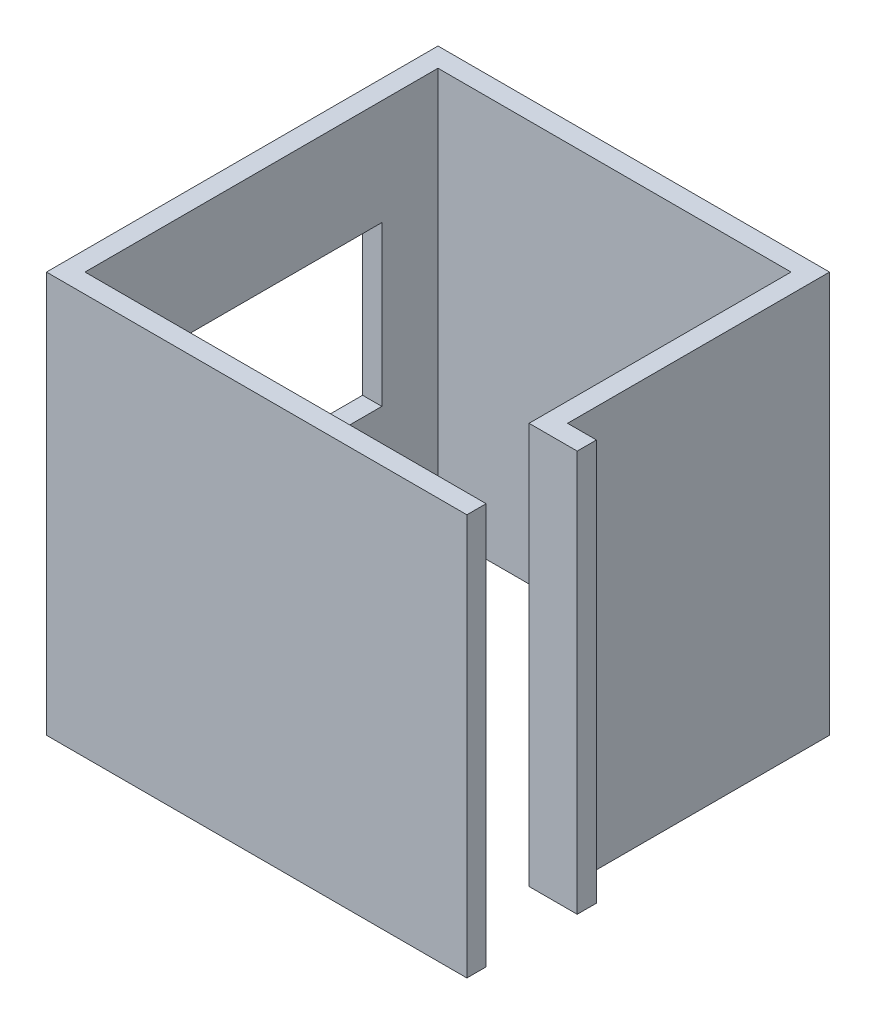
SolidWorks part; units mm, degrees
ref_plane "Спереди" through (0, 0, 0) normal (0, 0, 1) x (1, 0, 0)
ref_plane "Сверху" through (0, 0, 0) normal (0, 1, 0) x (1, 0, 0)
ref_plane "Справа" through (0, 0, 0) normal (1, 0, 0) x (0, 0, -1)
sketch "Эскиз1" plane through (0, 0, 0) normal (0, 1, 0) x (1, 0, 0)
  line L0 (0, 0) -> (0, 2200)
  line L1 (0, 2200) -> (2200, 2200)
  line L2 (2200, 2200) -> (2200, 567.5192)
  line L3 (2200, 567.5192) -> (2500, 567.5192)
  line L4 (0, 0) -> (2500, 0)
  point P4 (282.3103, 2180.8038)
  point P8 (0, 0)
  point P9 (0, 0)
  point P10 (2300, 0)
  point P11 (0, 0)
  point P12 (0, 0)
  point P13 (2500, 0)
extrude "Вытянуть-Тонкостенный1" add sketch "Эскиз1" along normal blind 2500 thin thin type one direction wall 120
sketch "Эскиз2" plane through (-120, 0, 0) normal (-1, 0, 0) x (0, 0, 1)
  line L1 (-1850, 1842.1461) -> (-650, 1842.1461)
  line L2 (-1850, 1842.1461) -> (-1850, 850)
  line L3 (-1850, 850) -> (-650, 850)
  line L4 (-650, 1842.1461) -> (-650, 850)
  point P4 (-1830.5849, 729.9818)
  point P5 (-636.986, 727.655)
  point P6 (0, 0)
extrude "Вырез-Вытянуть1" cut sketch "Эскиз2" against normal up to next
